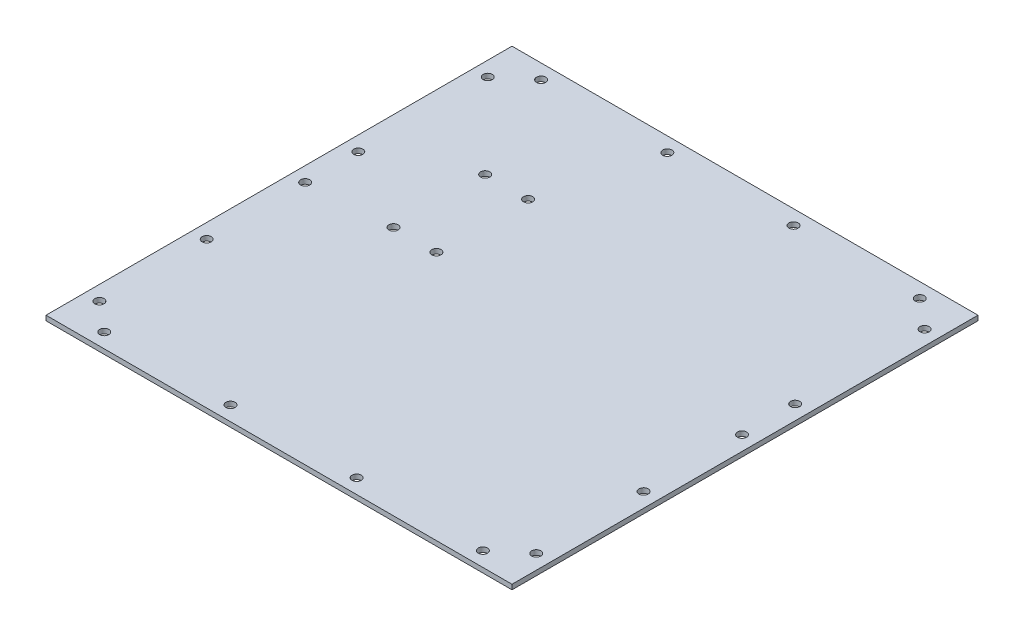
SolidWorks part; units mm, degrees
material "Thornel VCB-20 Carbon Cloth"
ref_plane "Front Plane" through (0, 0, 0) normal (0, 0, 1) x (1, 0, 0)
ref_plane "Top Plane" through (0, 0, 0) normal (0, 1, 0) x (1, 0, 0)
ref_plane "Right Plane" through (0, 0, 0) normal (1, 0, 0) x (0, 0, -1)
sketch "Sketch2" plane through (0, 0, 0) normal (0, 1, 0) x (1, 0, 0)
  line L0 (0, 0) -> (152.4, 0)
  line L1 (152.4, 0) -> (152.4, 152.4)
  line L2 (152.4, 152.4) -> (0, 152.4)
  line L3 (0, 152.4) -> (0, 0)
  dimension "D1" = 152.4
  dimension "D2" = 152.4
extrude "Boss-Extrude1" add sketch "Sketch2" along normal blind 1.5875
sketch "Sketch3" plane through (0, 1.5875, 0) normal (0, 1, 0) x (1, 0, 0)
  line L0 (0, 152.4) -> (4.7625, 152.4)
  line L1 (152.4, 152.4) -> (0, 152.4) construction
  line L2 (4.7625, 152.4) -> (4.7625, 0)
  line L3 (0, 0) -> (152.4, 0) construction
  line L4 (0, 152.4) -> (0, 147.6375)
  line L5 (0, 152.4) -> (0, 0) construction
  line L6 (0, 147.6375) -> (152.4, 147.6375)
  line L7 (152.4, 0) -> (152.4, 152.4) construction
  line L8 (152.4, 152.4) -> (147.6375, 152.4)
  line L9 (147.6375, 152.4) -> (147.6375, 0)
  line L10 (152.4, 0) -> (152.4, 4.7625)
  line L11 (152.4, 4.7625) -> (0, 4.7625)
  point P21 (4.7625, 139.7)
  point P23 (14.2875, 147.6375)
  point P24 (147.6375, 139.7)
  point P25 (138.1125, 4.7625)
  point P26 (4.7625, 12.7)
  dimension "D1" = 4.7625
  dimension "D2" = 4.7625
  dimension "D3" = 4.7625
  dimension "D4" = 4.7625
  dimension "D5" = 12.7
  dimension "D6" = 14.2875
  dimension "D7" = 12.7
  dimension "D8" = 14.2875
  dimension "D9" = 12.7
sketch "Sketch4" plane through (0, 1.5875, 0) normal (0, 1, 0) x (1, 0, 0)
  point P0 (14.2875, 147.6375)
  point P3 (147.6375, 139.7)
  point P6 (138.1125, 4.7625)
  point P9 (4.7625, 12.7)
sketch "Sketch6" plane through (0, 1.5875, 0) normal (0, 1, 0) x (1, 0, 0)
  line L0 (152.4, 4.7625) -> (0, 4.7625) construction
  line L1 (0, 152.4) -> (0, 0) construction
  point P0 (14.2875, 147.6375)
  point P3 (14.2875, 4.7625)
  dimension "D1" = 14.2875
hole_wizard "Ø3.0mm Dowel Hole2" positions "Sketch6" profile "Sketch7" hole size "Ø3.0" standard "ANSI Metric" end condition through all
sketch "Sketch7" plane through (14.2875, 1.5875, -147.6375) normal (1, 0, 0) x (0, 0, 1)
  line L0 (0, 0) -> (0, 1.5875)
  line L1 (0, 1.5875) -> (1.5, 1.5875)
  line L2 (1.5, 1.5875) -> (1.5, 0)
  line L5 (1.5, 0) -> (0, 0)
  line L11 (0, -6.35) -> (0, 107.95) construction
  dimension "Thru Hole Dia." = 3
  dimension "Thru Hole Depth" = 1.5875
sketch "Sketch8" plane through (0, 1.5875, 0) normal (0, 1, 0) x (1, 0, 0)
  point P0 (4.7625, 139.7)
  point P3 (147.6375, 139.7)
hole_wizard "Ø3.0mm Dowel Hole3" positions "Sketch8" profile "Sketch9" hole size "Ø3.0" standard "ANSI Metric" end condition through all
sketch "Sketch9" plane through (4.7625, 1.5875, -139.7) normal (1, 0, 0) x (0, 0, 1)
  line L0 (0, 0) -> (0, 1.5875)
  line L1 (0, 1.5875) -> (1.5, 1.5875)
  line L2 (1.5, 1.5875) -> (1.5, 0)
  line L5 (1.5, 0) -> (0, 0)
  line L11 (0, -6.35) -> (0, 107.95) construction
  dimension "Thru Hole Dia." = 3
  dimension "Thru Hole Depth" = 1.5875
pattern_linear "LPattern1" count 4 spacing 42.3333 along (0, 0, 1) skipping (2, 0) of "Ø3.0mm Dowel Hole3"
pattern_linear "LPattern2" count 4 spacing 41.275 along (1, 0, 0) of "Ø3.0mm Dowel Hole2"
sketch "Sketch10" plane through (0, 1.5875, 0) normal (0, 1, 0) x (1, 0, 0)
  line L1 (0, 0) -> (152.4, 0) construction
  point P1 (147.6375, 47.79)
  point P5 (147.6375, 80)
  dimension "D1" = 32.21
  dimension "D2" = 80
hole_wizard "Ø3.0mm Dowel Hole1" positions "Sketch10" profile "Sketch11" hole size "Ø3.0" standard "ANSI Metric" end condition through all
sketch "Sketch11" plane through (147.6375, 1.5875, -47.79) normal (1, 0, 0) x (0, 0, 1)
  line L0 (0, 0) -> (0, 1.5875)
  line L1 (0, 1.5875) -> (1.5, 1.5875)
  line L2 (1.5, 1.5875) -> (1.5, 0)
  line L5 (1.5, 0) -> (0, 0)
  line L11 (0, -6.35) -> (0, 107.95) construction
  dimension "Thru Hole Dia." = 3
  dimension "Thru Hole Depth" = 1.5875
ref_plane "Plane1" through (76.2, 0, 0) normal (1, 0, 0) x (0, 0, -1)
mirror "Mirror1" about plane through (76.2, 0, 0) normal (1, 0, 0) of "Ø3.0mm Dowel Hole1"
sketch "Sketch12" plane through (0, 1.5875, 0) normal (0, 1, 0) x (1, 0, 0)
  circle A0 centre (31.9494, 111.6806) radius 1.5
  circle A1 centre (45.9994, 111.6806) radius 1.5
  circle A2 centre (31.9494, 81.6806) radius 1.5
  circle A3 centre (45.9994, 81.6806) radius 1.5
  point P12 (0, 0)
extrude "Cut-Extrude1" cut sketch "Sketch12" against normal blind 10 contours A1 | A0 | A2 | A3 | A0 region at (31.9494, 1.5875, -111.6806) region at (45.9994, 1.5875, -111.6806) region at (31.9494, 1.5875, -81.6806) region at (45.9994, 1.5875, -81.6806)
